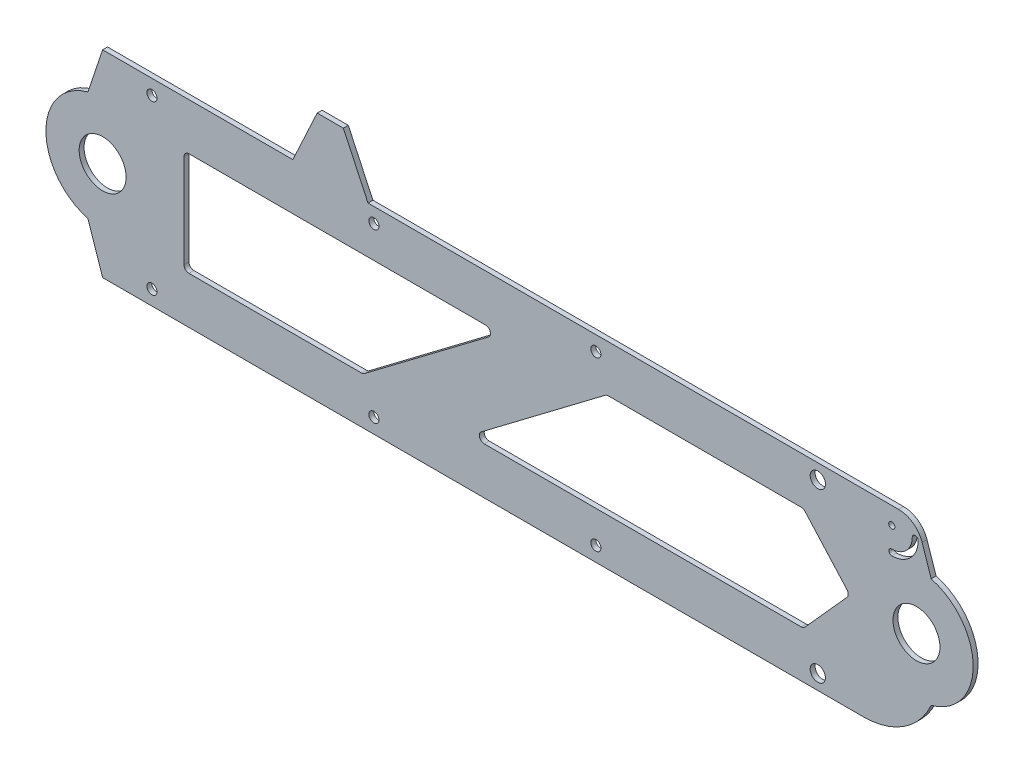
SolidWorks part; units mm, degrees
ref_plane "前视基准面" through (0, 0, 0) normal (0, 0, 1) x (1, 0, 0)
ref_plane "上视基准面" through (0, 0, 0) normal (0, 1, 0) x (1, 0, 0)
ref_plane "右视基准面" through (0, 0, 0) normal (1, 0, 0) x (0, 0, -1)
sketch "草图1" plane through (0, 0, 0) normal (0, 0, 1) x (1, 0, 0)
  line L0 (328.5429, -0.1457) -> (-1.4571, -0.1457) construction
  line L8 (328.5429, -40.1457) -> (-1.4571, -40.1457)
  line L9 (-1.4571, 39.8543) -> (328.5429, 39.8543) construction
  line L10 (328.5429, -0.1457) -> (340.7951, 45.5801) construction
  line L11 (328.5429, -0.1457) -> (340.7951, -45.8715) construction
  line L14 (334.4957, 22.0706) -> (328.5429, 39.8543)
  line L17 (334.4957, -22.362) -> (328.5429, -40.1457)
  line L18 (163.5429, -0.1457) -> (163.5429, 12.1844) construction
  line L19 (-1.4571, 39.8543) -> (-7.41, 22.0706)
  line L20 (-7.41, -22.362) -> (-1.4571, -40.1457)
  line L34 (96.1749, 61.1543) -> (106.1459, 39.8543)
  line L35 (96.1749, 61.1543) -> (85.5444, 61.1543)
  line L36 (85.5444, 61.1543) -> (75.6844, 39.8543)
  line L37 (75.6844, 39.8543) -> (-1.4571, 39.8543)
  line L38 (106.1459, 39.8543) -> (321.0716, 39.8543)
  line L41 (356.5429, 50.4301) -> (356.5429, 24.1217) construction
  line L42 (321.0716, 39.8543) -> (356.5429, 39.8543) construction
  line L44 (356.5429, 24.1217) -> (347.9586, 12.1844) construction
  line L45 (321.0716, 39.8543) -> (328.5429, 39.8543)
  circle A0 centre (-1.4571, -0.1457) radius 9.52
  circle A1 centre (-1.4571, -0.1457) radius 40 construction
  circle A11 centre (328.5429, -0.1457) radius 9.52
  circle A12 centre (328.5429, -0.1457) radius 40 construction
  circle A16 centre (328.5429, -0.1457) radius 23 construction
  circle A25 centre (318.5429, 32.8543) radius 1.25
  circle A26 centre (318.5429, 32.8543) radius 9.5 construction
  arc A27 (318.5429, 23.3543) -> (328.0429, 32.8543) centre (318.5429, 32.8543) ccw construction
  arc A37 (-7.41, -22.362) -> (-7.41, 22.0706) centre (-1.4571, -0.1457) cw
  arc A40 (334.4957, 22.0706) -> (334.4957, -22.362) centre (328.5429, -0.1457) cw
  arc A41 (318.5429, 22.1543) -> (329.2429, 32.8543) centre (318.5429, 32.8543) ccw
  arc A42 (318.5429, 24.5543) -> (326.8429, 32.8543) centre (318.5429, 32.8543) ccw
  arc A43 (318.5429, 24.5543) -> (318.5429, 22.1543) centre (318.5429, 23.3543) ccw
  arc A44 (329.2429, 32.8543) -> (326.8429, 32.8543) centre (328.0429, 32.8543) ccw
  point P10 (325.2604, 26.1368)
  dimension "D1" = 330
  dimension "D2" = 19.04
  dimension "D3" = 2.5
  dimension "D4" = 19.04
  dimension "D5" = 80
  dimension "D6" = 7
  dimension "D7" = 19
  dimension "D8" = 105
  dimension "D9" = 10
extrude "凸台-拉伸1" add sketch "草图1" along normal blind 2
sketch "草图2" plane through (0, 0, 2) normal (0, 0, 1) x (1, 0, 0)
  line L0 (198.5429, 33.8543) -> (288.5429, 33.8543) construction
  line L1 (18.5429, 33.8543) -> (198.5429, 33.8543) construction
  line L2 (108.5429, -34.1457) -> (198.5429, 33.8543) construction
  line L3 (18.5429, 33.8543) -> (18.5429, -34.1457) construction
  line L4 (18.5429, -34.1457) -> (108.5429, -34.1457) construction
  line L5 (31.5429, -21.1457) -> (104.1839, -21.1457)
  line L6 (104.1839, -21.1457) -> (159.7721, 20.8543)
  line L7 (31.5429, 20.8543) -> (159.7721, 20.8543)
  line L8 (31.5429, 20.8543) -> (31.5429, -21.1457)
  line L9 (108.5429, -34.1457) -> (288.5429, -34.1457) construction
  line L20 (288.5429, 33.8543) -> (319.0229, -0.1457) construction
  line L28 (147.3136, -21.1457) -> (202.9018, 20.8543)
  line L31 (319.0229, -0.1457) -> (288.5429, -34.1457) construction
  line L40 (202.9018, 20.8543) -> (282.7379, 20.8543)
  line L41 (282.7379, 20.8543) -> (301.5638, -0.1457)
  line L42 (301.5638, -0.1457) -> (282.7379, -21.1457)
  line L43 (18.5429, 33.8543) -> (-161.4571, 33.8543) construction
  line L54 (147.3136, -21.1457) -> (282.7379, -21.1457)
  circle A1 centre (108.5429, 33.8543) radius 2.05
  circle A2 centre (198.5429, 33.8543) radius 2.05
  circle A3 centre (288.5429, 33.8543) radius 2.05 construction
  circle A4 centre (108.5429, -34.1457) radius 2.05
  circle A5 centre (198.5429, -34.1457) radius 2.05
  circle A6 centre (288.5429, -34.1457) radius 2.05 construction
  circle A7 centre (18.5429, -34.1457) radius 2.05
  circle A10 centre (18.5429, 33.8543) radius 2.05
  circle A11 centre (328.5429, -0.1457) radius 9.52 construction
  circle A12 centre (288.5429, 33.8543) radius 3.1
  circle A13 centre (288.5429, -34.1457) radius 3.1
  point P2 (-1.4571, -0.1457)
  dimension "D1" = 13
  dimension "D2" = 34
  dimension "D6" = 13
extrude "切除-拉伸1" cut sketch "草图2" against normal blind 4
fillet "圆角1" radius 2 9 edges at (104.1839, -21.1457, 1) (159.7721, 20.8543, 1) (31.5429, -21.1457, 1) (31.5429, 20.8543, 1) (202.9018, 20.8543, 1) (282.7379, 20.8543, 1) (282.7379, -21.1457, 1) (301.5638, -0.1457, 1) (147.3136, -21.1457, 1)
fillet "圆角3" radius 30 1 edges at (328.5429, -40.1457, 1)
fillet "圆角6" radius 10 1 edges at (328.5429, 39.8543, 1)
